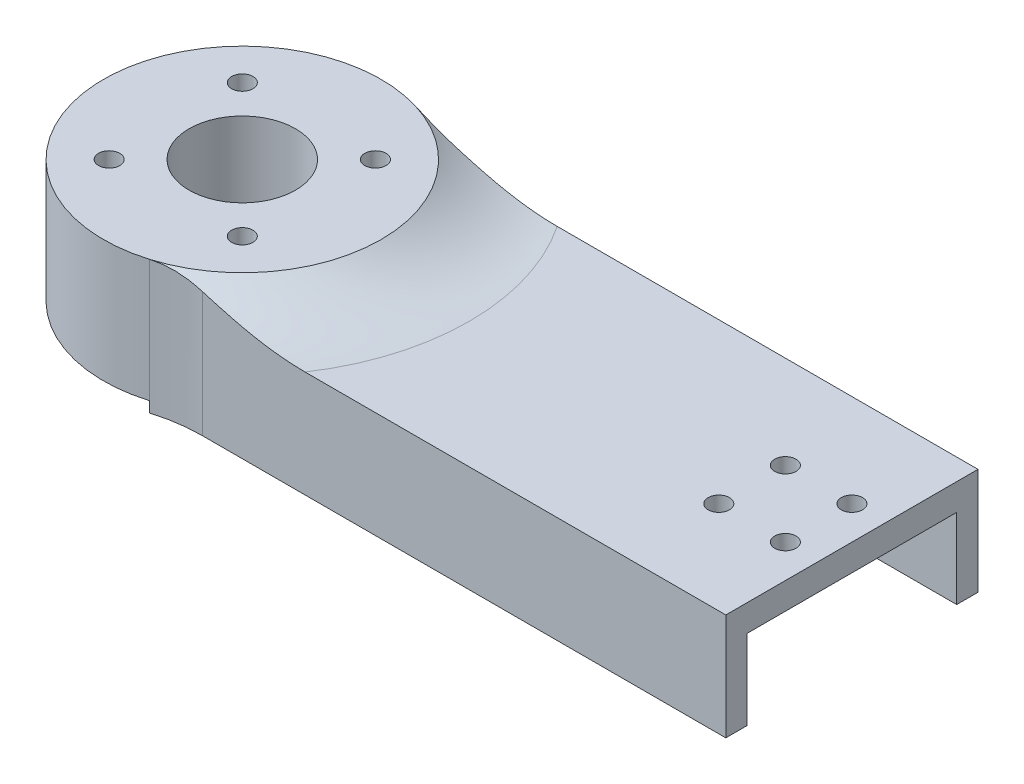
SolidWorks part; units mm, degrees
ref_plane "Front Plane" through (0, 0, 0) normal (0, 0, 1) x (1, 0, 0)
ref_plane "Top Plane" through (0, 0, 0) normal (0, 1, 0) x (1, 0, 0)
ref_plane "Right Plane" through (0, 0, 0) normal (1, 0, 0) x (0, 0, -1)
sketch "Sketch1" plane through (0, 0, 0) normal (0, 1, 0) x (1, 0, 0)
  line L1 (-50.3006, 19.6842) -> (50.3006, 19.6842)
  line L3 (-50.3006, -19.6842) -> (50.3006, -19.6842)
  line L5 (-50.3006, 19.6842) -> (50.3006, -19.6842) construction
  line L6 (-50.3006, -19.6842) -> (50.3006, 19.6842) construction
  line L9 (44.9237, -17.58) -> (39.4721, -17.58)
  line L11 (-50.3006, 0) -> (35, 0) construction
  line L12 (35, 0) -> (43.9443, 0) construction
  line L13 (39.4721, 0) -> (39.4721, -17.58) construction
  line L14 (39.4721, -8.79) -> (28.2221, -8.79) construction
  line L15 (50.3006, 19.6842) -> (50.3006, -19.6842)
  line L16 (-50.3006, 19.6842) -> (-50.3006, -19.6842) construction
  circle A0 centre (33.8471, -8.79) radius 2
  circle A1 centre (45.0971, -8.79) radius 2
  circle A2 centre (45.0971, 8.79) radius 2
  circle A3 centre (33.8471, 8.79) radius 2
  arc A6 (-50.3006, 19.6842) -> (-50.3006, -19.6842) centre (-61.1994, 0) ccw
  point P0 (0, 0)
  point P6 (-83.6994, 0)
  dimension "D3" = 5.2035
  dimension "D4" = 16.4535
  dimension "D1" = 45
  dimension "D2" = 134
extrude "Boss-Extrude2" add sketch "Sketch1" along normal blind 5
sketch "Sketch8" plane through (0, 5, 0) normal (0, 1, 0) x (1, 0, 0)
  line L0 (-50.3006, -19.6842) -> (50.3006, -19.6842) construction
  line L1 (-50.3006, 19.6842) -> (50.3006, 19.6842) construction
  line L2 (-50.3006, -19.6842) -> (50.3006, -19.6842)
  line L3 (-50.3006, 19.6842) -> (50.3006, 19.6842)
  line L4 (-50.3006, 23.6842) -> (50.3006, 23.6842)
  line L5 (-50.3006, -23.6842) -> (50.3006, -23.6842)
  line L6 (50.3006, 23.6842) -> (50.3006, 19.6842)
  line L7 (50.3006, -19.6842) -> (50.3006, -23.6842)
  line L8 (-50.3006, -19.6842) -> (-50.3006, -23.6842)
  line L9 (-50.3006, 23.6842) -> (-50.3006, 19.6842)
  dimension "D1" = 4
  dimension "D2" = 4
extrude "Boss-Extrude8" add sketch "Sketch8" along normal blind 15 and the other way up to surface other way up to face at (33.8471, 0, -6.79)
sketch "Sketch9" plane through (0, 5, 0) normal (0, 1, 0) x (1, 0, 0)
  circle A0 centre (-61.1994, 0) radius 26.0715
extrude "Boss-Extrude9" add sketch "Sketch9" along normal blind 15 and the other way blind 10
fillet "Fillet2" radius 30 3 edges at (-35.1279, 0, 0) (-50.3006, 10, -23.6842) (-50.3006, 10, 23.6842)
sketch "Sketch10" plane through (50.3006, 0, 0) normal (1, 0, 0) x (0, 0, -1)
  line L0 (-23.6842, 20) -> (-19.6842, 20) construction
  line L1 (-19.6842, 5) -> (-19.6842, 20) construction
  line L2 (19.6842, 5) -> (-19.6842, 5) construction
  line L3 (19.6842, 5) -> (19.6842, 20) construction
  line L4 (19.6842, 20) -> (23.6842, 20) construction
  line L5 (23.6842, 0) -> (23.6842, 20) construction
  line L6 (23.6842, 0) -> (-23.6842, 0) construction
  line L7 (-23.6842, 20) -> (-23.6842, -3.4498) construction
  line L8 (-23.6842, 20) -> (-19.6842, 20)
  line L9 (-19.6842, 5) -> (-19.6842, 20)
  line L10 (19.6842, 5) -> (-19.6842, 5)
  line L11 (19.6842, 5) -> (19.6842, 20)
  line L12 (19.6842, 20) -> (23.6842, 20)
  line L13 (23.6842, 0) -> (23.6842, 20)
  line L14 (23.6842, 0) -> (-23.6842, 0)
  line L15 (-23.6842, 20) -> (-23.6842, 0)
extrude "Boss-Extrude10" add sketch "Sketch10" along normal blind 3
sketch "Sketch11" plane through (0, 20, 0) normal (0, 1, 0) x (1, 0, 0)
  line L0 (-21.1994, 7.2319) -> (-52.9109, 7.2319)
  line L1 (-61.1994, 0) -> (0, 0) construction
  line L2 (-21.1994, -7.2319) -> (-52.9109, -7.2319)
  line L3 (-21.1994, 7.2319) -> (-21.1994, -7.2319)
  arc A0 (-52.9109, 7.2319) -> (-52.9109, -7.2319) centre (-61.1994, 0) ccw
  dimension "D1" = 40
  dimension "D2" = 22
extrude "Cut-Extrude3" cut sketch "Sketch11" against normal up to surface (15 mm away) up to face at (6.8424, 5, 0)
sketch "Sketch12" plane through (0, 20, 0) normal (0, 1, 0) x (1, 0, 0)
  line L0 (-73.6994, -10.5) -> (-73.6994, -12.5) construction
  line L5 (-73.6994, 12.5) -> (-48.6994, -12.5) construction
  line L6 (-73.6994, -12.5) -> (-48.6994, 12.5) construction
  line L7 (-73.6994, 12.5) -> (-48.6994, 12.5) construction
  line L8 (-73.6994, 12.5) -> (-73.6994, 10.5) construction
  line L9 (-73.6994, -12.5) -> (-48.6994, -12.5) construction
  line L10 (-48.6994, 12.5) -> (-48.6994, -12.5) construction
  line L11 (-73.6994, 12.5) -> (-48.6994, -12.5) construction
  line L12 (-73.6994, -12.5) -> (-48.6994, 12.5) construction
  circle A0 centre (-48.6994, 12.5) radius 2
  circle A1 centre (-48.6994, -12.5) radius 2
  circle A3 centre (-73.6994, 12.5) radius 2
  circle A4 centre (-73.6994, -12.5) radius 2
  point P0 (-61.1994, 0)
  point P9 (-61.1994, 0)
  dimension "D1" = 25
  dimension "D2" = 25
  dimension "D4" = 25
extrude "Cut-Extrude4" cut sketch "Sketch12" against normal through all
ref_plane "Plane2" through (0, 30, 0) normal (0, 1, 0) x (1, 0, 0)
mirror "Mirror2" about plane through (0, 30, 0) normal (0, 1, 0) of bodies 113
sketch "Sketch13" plane through (0, 30, 0) normal (0, 1, 0) x (1, 0, 0)
  line L1 (-158.462, 40.0477) -> (125.2403, 40.0477)
  line L2 (-158.462, 40.0477) -> (-158.462, -44.7885)
  line L3 (-158.462, -44.7885) -> (125.2403, -44.7885)
  line L4 (125.2403, 40.0477) -> (125.2403, -44.7885)
extrude "Cut-Extrude5" cut sketch "Sketch13" against normal through all
sketch "Sketch14" plane through (0, 40, 0) normal (0, -1, 0) x (1, 0, 0)
  line L0 (-52.9109, -7.2319) -> (-36.151, -7.2319) construction
  line L1 (-52.9109, 7.2319) -> (-36.151, 7.2319) construction
  line L2 (-52.9109, -7.2319) -> (-36.151, -7.2319)
  line L3 (-52.9109, 7.2319) -> (-36.151, 7.2319)
  arc A0 (-52.9109, -7.2319) -> (-52.9109, 7.2319) centre (-61.1994, 0) ccw
  arc A1 (-36.151, -7.2319) -> (-36.151, 7.2319) centre (-61.1994, 0) ccw
extrude "Boss-Extrude11" add sketch "Sketch14" against normal up to surface (15 mm away) up to face at (-22.1522, 55, 0)
sketch "Sketch15" plane through (0, 40, 0) normal (0, -1, 0) x (1, 0, 0)
  circle A0 centre (-61.1994, 0) radius 10
extrude "Cut-Extrude6" cut sketch "Sketch15" against normal through all
sketch "Sketch16" plane through (0, 60, 0) normal (0, 1, 0) x (1, 0, 0)
  circle A0 centre (33.8471, -8.79) radius 2 construction
  circle A1 centre (45.0971, -8.79) radius 2 construction
  circle A2 centre (45.0971, 8.79) radius 2 construction
  circle A3 centre (33.8471, 8.79) radius 2 construction
  circle A4 centre (33.8471, -8.79) radius 2
  circle A5 centre (45.0971, -8.79) radius 2
  circle A6 centre (45.0971, 8.79) radius 2
  circle A7 centre (33.8471, 8.79) radius 2
extrude "Boss-Extrude12" add sketch "Sketch16" against normal up to surface (5 mm away) up to face at (6.8424, 55, 0)
sketch "Sketch17" plane through (0, 55, 0) normal (0, -1, 0) x (1, 0, 0)
  line L0 (53.3006, -19.6842) -> (53.3006, 19.6842) construction
  line L1 (28.3006, 12.5) -> (53.3006, 12.5) construction
  line L2 (28.3006, 12.5) -> (28.3006, -12.5) construction
  line L3 (28.3006, -12.5) -> (53.3006, -12.5) construction
  line L4 (53.3006, 12.5) -> (53.3006, -12.5) construction
  line L5 (-61.1994, 0) -> (53.3006, 0) construction
  line L6 (40.8006, 12.5) -> (40.8006, 0) construction
  line L7 (40.8006, 6.25) -> (28.3006, 6.25) construction
  circle A0 centre (34.5506, 6.25) radius 2
  circle A1 centre (47.0506, 6.25) radius 2
  circle A2 centre (47.0506, -6.25) radius 2
  circle A3 centre (34.5506, -6.25) radius 2
  dimension "D1" = 25
  dimension "D2" = 25
extrude "Cut-Extrude7" cut sketch "Sketch17" against normal through all
sketch "Sketch19" plane through (0, 40, 0) normal (0, -1, 0) x (1, 0, 0)
  circle A0 centre (-61.1994, 0) radius 26.0715
extrude "Cut-Extrude9" cut sketch "Sketch19" against normal blind 2
sketch "Sketch21" plane through (0, 42, 0) normal (0, -1, 0) x (1, 0, 0)
  circle A0 centre (-61.1994, 0) radius 11
  circle A1 centre (-61.1994, 0) radius 10
extrude "Boss-Extrude13" add sketch "Sketch21" against normal up to surface (13 mm away) up to face at (34.5506, 55, -4.25)
